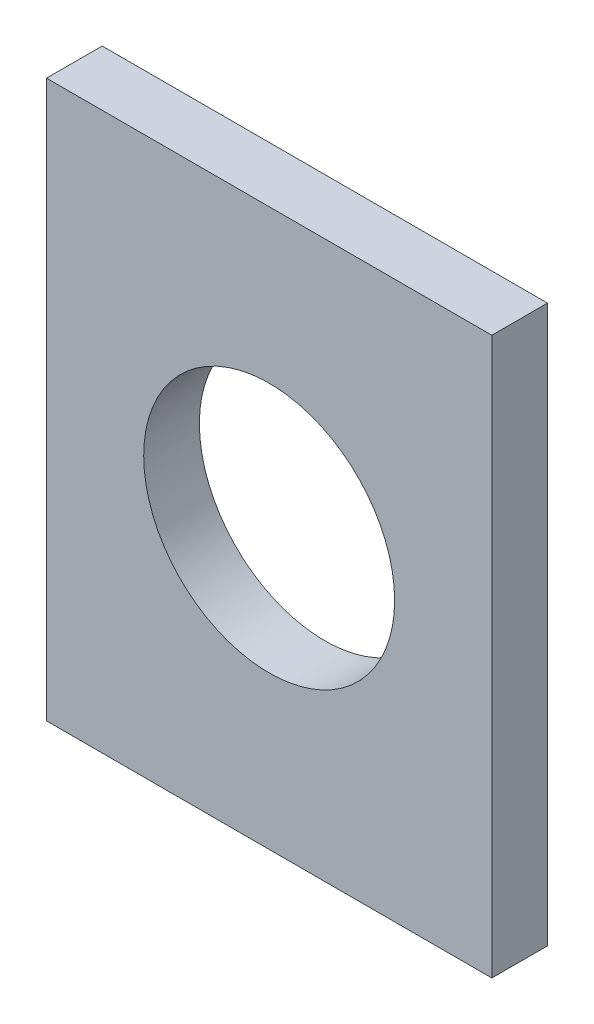
SolidWorks part; units mm, degrees
material "6061 Alloy"
ref_plane "Front" through (0, 0, 0) normal (0, 0, 1) x (1, 0, 0)
ref_plane "Top" through (0, 0, 0) normal (0, 1, 0) x (1, 0, 0)
ref_plane "Right" through (0, 0, 0) normal (1, 0, 0) x (0, 0, -1)
sketch "Sketch1" plane through (0, 0, 0) normal (0, 0, 1) x (1, 0, 0)
  line L0 (50.8, 63.5) -> (0, 0) construction
  line L1 (0, 0) -> (50.8, 0)
  line L2 (0, 0) -> (0, 63.5)
  line L3 (0, 63.5) -> (50.8, 63.5)
  line L4 (50.8, 0) -> (50.8, 63.5)
  line L5 (0, 63.5) -> (50.8, 0) construction
  circle A0 centre (25.4, 31.75) radius 14.3129
  dimension "D3" = 28.6258
  dimension "D1" = 50.8
  dimension "D2" = 31.75
extrude "Boss-Extrude1" add sketch "Sketch1" along normal blind 6.35
